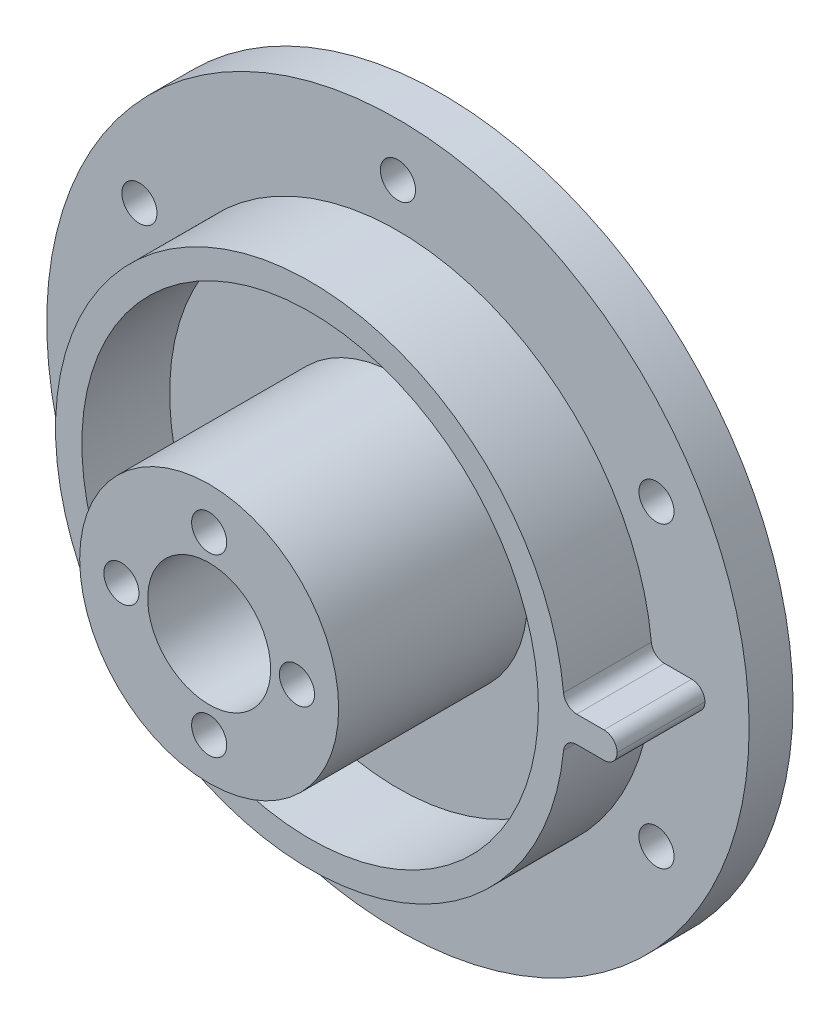
SolidWorks part; units mm, degrees
ref_plane "Plano frontal" through (0, 0, 0) normal (0, 0, 1) x (1, 0, 0)
ref_plane "Plano superior" through (0, 0, 0) normal (0, 1, 0) x (1, 0, 0)
ref_plane "Plano direito" through (0, 0, 0) normal (1, 0, 0) x (0, 0, -1)
sketch "Esboço1" plane through (0, 0, 0) normal (0, 0, 1) x (1, 0, 0)
  circle A0 centre (0, 0) radius 40
  circle A1 centre (0, 34) radius 2
  circle A2 centre (29.4449, 17) radius 2
  circle A3 centre (29.4449, -17) radius 2
  circle A4 centre (0, -34) radius 2
  circle A5 centre (-29.4449, -17) radius 2
  circle A6 centre (-29.4449, 17) radius 2
  point P18 (0, 0)
  dimension "D1" = 80
  dimension "D2" = 4
  dimension "D3" = 34
  dimension "D4" = 6
extrude "Ressalto-extrusão1" add sketch "Esboço1" along normal blind 5
sketch "Esboço2" plane through (0, 0, 5) normal (0, 0, 1) x (1, 0, 0)
  circle A0 centre (0, 0) radius 14.75
  dimension "D1" = 29.5
extrude "Ressalto-extrusão2" add sketch "Esboço2" along normal blind 21.5
sketch "Esboço3" plane through (0, 0, 26.5) normal (0, 0, 1) x (1, 0, 0)
  circle A0 centre (0, 10) radius 2
  circle A1 centre (10, 0) radius 2
  circle A2 centre (0, -10) radius 2
  circle A3 centre (-10, 0) radius 2
  circle A4 centre (0, 0) radius 7
  point P12 (0, 0)
  dimension "D1" = 4
  dimension "D2" = 10
  dimension "D4" = 14
  dimension "D3" = 4
extrude "Corte-extrusão1" cut sketch "Esboço3" against normal up to surface (26.5 mm away) up to face at (40, 0, 0)
sketch "Esboço4" plane through (0, 0, 5) normal (0, 0, 1) x (1, 0, 0)
  line L0 (34.9612, -1.5) -> (28.9612, -1.5)
  line L1 (34.9612, 1.5) -> (34.9612, -1.5)
  line L2 (34.9612, 1.5) -> (28.9612, 1.5)
  circle A0 centre (0, 0) radius 26
  arc A1 (28.9612, 1.5) -> (28.9612, -1.5) centre (0, 0) ccw
  point P9 (34.9612, 0)
  dimension "D1" = 52
  dimension "D2" = 58
  dimension "D3" = 6
  dimension "D4" = 3
extrude "Ressalto-extrusão3" add sketch "Esboço4" along normal blind 10
fillet "Filete1" radius 1.5 4 edges at (28.9612, 1.5, 10) (28.9612, -1.5, 10) (34.9612, 1.5, 10) (34.9612, -1.5, 10)
